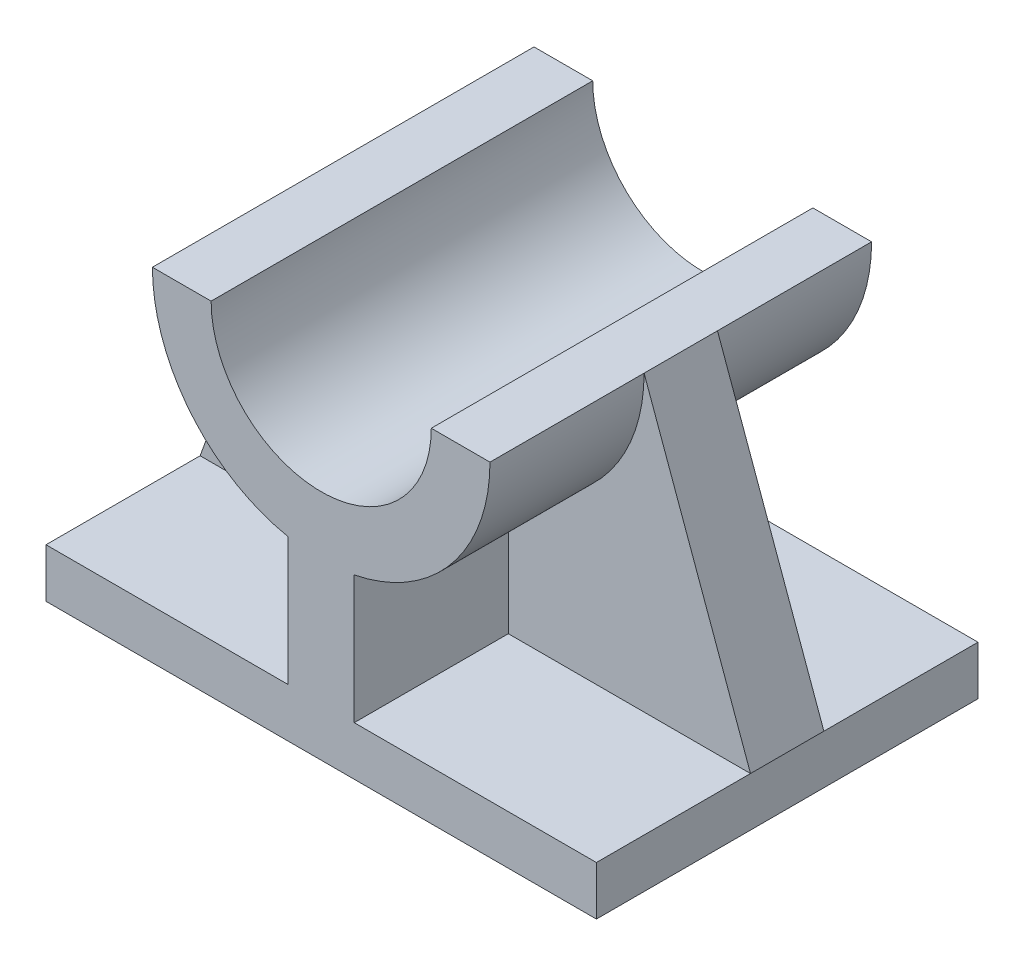
SolidWorks part; units mm, degrees
ref_plane "Front Plane" through (0, 0, 0) normal (0, 0, 1) x (1, 0, 0)
ref_plane "Top Plane" through (0, 0, 0) normal (0, 1, 0) x (1, 0, 0)
ref_plane "Right Plane" through (0, 0, 0) normal (1, 0, 0) x (0, 0, -1)
sketch "Sketch1" plane through (0, 0, 0) normal (0, 0, 1) x (1, 0, 0)
  line L0 (42, 6.6786) -> (75, 6.6786)
  line L1 (0, 0) -> (75, 0)
  line L2 (0, 0) -> (0, 6.6786)
  line L4 (75, 0) -> (75, 6.6786)
  line L9 (42, 6.6786) -> (42, 24.1231)
  line L10 (33, 6.6786) -> (33, 24.1231)
  line L11 (60.5, 46.6786) -> (52.5, 46.6786)
  line L12 (22.5, 46.6786) -> (14.5, 46.6786)
  line L13 (60.5, 46.6786) -> (75, 6.6786)
  line L14 (14.5, 46.6786) -> (0, 6.6786)
  line L15 (0, 6.6786) -> (33, 6.6786)
  arc A4 (14.5, 46.6786) -> (33, 24.1231) centre (37.5, 46.6786) ccw
  arc A5 (22.5, 46.6786) -> (52.5, 46.6786) centre (37.5, 46.6786) ccw
  arc A6 (42, 24.1231) -> (60.5, 46.6786) centre (37.5, 46.6786) ccw
  point P16 (37.5, 46.6786)
  dimension "D4" = 40
  dimension "D5" = 46
  dimension "D6" = 30
  dimension "D1" = 33
  dimension "D2" = 75
  dimension "D3" = 33
  dimension "D7" = 40
  dimension "D8" = 40
extrude "Boss-Extrude1" add sketch "Sketch1" along normal mid plane 52 contours L9 A6 L11 A5 L12 A4 L10 L15 L2 L1 L4 L0 region at (37.5, 18.0582, 0)
extrude "Boss-Extrude2" add sketch "Sketch1<3>" along normal mid plane 10 contours A6 L9 L0 L13 | A4 L14 L15 L10 region at (57.6038, 19.2827, 0) region at (17.3962, 19.2827, 0)
sketch "Sketch1<3>" plane through (0, 0, 0) normal (0, 0, 1) x (1, 0, 0) same geometry as "Sketch1"
